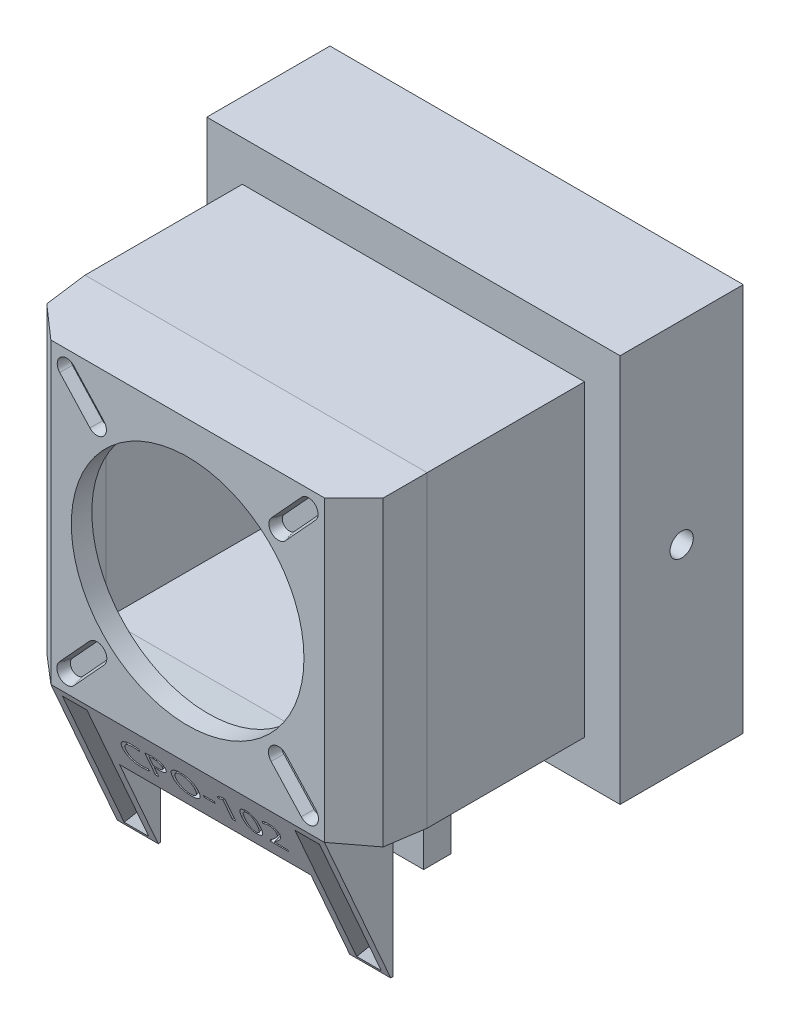
SolidWorks part; units mm, degrees
ref_plane "前视基准面" through (0, 0, 0) normal (0, 0, 1) x (1, 0, 0)
ref_plane "上视基准面" through (0, 0, 0) normal (0, 1, 0) x (1, 0, 0)
ref_plane "右视基准面" through (0, 0, 0) normal (1, 0, 0) x (0, 0, -1)
sketch "草图1" plane through (0, 0, 0) normal (0, 0, 1) x (1, 0, 0)
  line L1 (0, 0) -> (25, 0)
  line L2 (0, 0) -> (0, -22.5)
  line L3 (0, -22.5) -> (25, -22.5)
  line L4 (25, 0) -> (25, -22.5)
  dimension "D1" = 25
  dimension "D2" = 22.5
extrude "凸台-拉伸1" add sketch "草图1" along normal blind 5 draft 4
sketch "草图2" plane through (0, 0, 5) normal (0, 0, 1) x (1, 0, 0)
  line L0 (0.3496, -0.3496) -> (24.6504, -22.1504) construction
  circle A0 centre (12.5, -11.25) radius 8.5
  dimension "D1" = 17
sketch "草图3" plane through (0, 0, 0) normal (0, 0, -1) x (-1, 0, 0)
  line L4 (0, -22.5) -> (0, 0)
  line L5 (0, 0) -> (-25, 0)
  line L6 (-25, 0) -> (-25, -22.5)
  line L7 (-25, -22.5) -> (0, -22.5)
  line L8 (0, -22.5) -> (0, 0)
  line L9 (0, 0) -> (-25, 0)
  line L10 (-25, 0) -> (-25, -22.5)
  line L11 (-25, -22.5) -> (0, -22.5)
  dimension "D1" = 0
extrude "凸台-拉伸2" add sketch "草图3" along normal blind 2.5
chamfer "倒角2" distance 2 angle 45 2 edges at (24.6504, -11.25, 5) (0.3496, -11.25, 5) first distance on face at (24.8252, -11.25, 2.5) first distance on face at (0.1748, -11.25, 2.5)
shell "抽壳1" thickness 1.5 removed face at (12.5, -11.25, -2.5)
extrude "切除-拉伸1" cut sketch "草图2" against normal blind 5
sketch "草图4" plane through (0, 0, 5) normal (0, 0, 1) x (1, 0, 0)
  line L0 (22.4947, -0.3496) -> (2.5053, -22.1504) construction
  line L1 (2.5053, -22.1504) -> (12.5, -11.25) construction
  line L2 (12.5, -11.25) -> (12.5, -3.0139) construction
  line L3 (19.1306, -4.0187) -> (21.3352, -1.6142) construction
  line L4 (18.6184, -3.5491) -> (20.8231, -1.1446)
  line L5 (19.6427, -4.4882) -> (21.8473, -2.0838)
  line L6 (12.5, -11.25) -> (22.4947, -22.1504) construction
  line L7 (19.1306, -18.4813) -> (21.3352, -20.8858) construction
  line L8 (19.6635, -17.9926) -> (21.8682, -20.3971)
  line L9 (18.5976, -18.9701) -> (20.8022, -21.3745)
  line L10 (5.8694, -18.4813) -> (3.6648, -20.8858) construction
  line L11 (5.3365, -17.9926) -> (3.1318, -20.3971)
  line L12 (6.4024, -18.9701) -> (4.1978, -21.3745)
  line L13 (5.8694, -4.0187) -> (3.6648, -1.6142) construction
  line L14 (6.3816, -3.5491) -> (4.1769, -1.1446)
  line L15 (5.3573, -4.4882) -> (3.1527, -2.0838)
  arc A0 (18.6184, -3.5491) -> (19.6427, -4.4882) centre (19.1306, -4.0187) ccw
  arc A1 (21.8473, -2.0838) -> (20.8231, -1.1446) centre (21.3352, -1.6142) ccw
  arc A2 (19.6635, -17.9926) -> (18.5976, -18.9701) centre (19.1306, -18.4813) ccw
  arc A3 (20.8022, -21.3745) -> (21.8682, -20.3971) centre (21.3352, -20.8858) ccw
  arc A4 (5.3365, -17.9926) -> (6.4024, -18.9701) centre (5.8694, -18.4813) cw
  arc A5 (4.1978, -21.3745) -> (3.1318, -20.3971) centre (3.6648, -20.8858) cw
  arc A6 (6.3816, -3.5491) -> (5.3573, -4.4882) centre (5.8694, -4.0187) cw
  arc A7 (3.1527, -2.0838) -> (4.1769, -1.1446) centre (3.6648, -1.6142) cw
  point P8 (20.2329, -2.8164)
  point P17 (20.2329, -19.6836)
  point P24 (4.7671, -19.6836)
  point P31 (4.7671, -2.8164)
extrude "切除-拉伸2" cut sketch "草图4" against normal blind 0.8 draft 13
sketch "草图5" plane through (0, 0, -2.5) normal (0, 0, -1) x (-1, 0, 0)
  line L1 (-23.5, -1.5) -> (-1.5, -1.5)
  line L2 (-23.5, -1.5) -> (-23.5, -21)
  line L3 (-23.5, -21) -> (-1.5, -21)
  line L4 (-25, -22.5) -> (0, -22.5)
  line L5 (0, -22.5) -> (0, 0)
  line L6 (0, 0) -> (-25, 0)
  line L7 (-25, 0) -> (-25, -22.5)
  line L8 (-25, -22.5) -> (0, -22.5)
  line L9 (0, -22.5) -> (0, 0)
  line L10 (0, 0) -> (-25, 0)
  line L11 (-25, 0) -> (-25, -22.5)
  line L12 (-1.5, -1.5) -> (-1.5, -21)
  dimension "D1" = 0
extrude "凸台-拉伸3" add sketch "草图5" along normal blind 10
sketch "草图6" plane through (0, 0, -12.5) normal (0, 0, -1) x (-1, 0, 0)
  line L0 (-27.6, 2.95) -> (2.6, 2.95)
  line L1 (-26.1, 1.45) -> (1.1, 1.45)
  line L2 (-26.1, 1.45) -> (-26.1, -23.95)
  line L3 (-26.1, -23.95) -> (1.1, -23.95)
  line L4 (1.1, 1.45) -> (1.1, -23.95)
  line L5 (-26.1, 1.45) -> (1.1, -23.95) construction
  line L6 (-26.1, -23.95) -> (1.1, 1.45) construction
  line L7 (-23.5, -1.5) -> (-1.5, -1.5)
  line L8 (-23.5, -1.5) -> (-23.5, -21)
  line L9 (-23.5, -21) -> (-1.5, -21)
  line L10 (-1.5, -1.5) -> (-1.5, -21)
  line L11 (2.6, 2.95) -> (2.6, -25.45)
  line L12 (-27.6, -25.45) -> (2.6, -25.45)
  line L13 (-27.6, 2.95) -> (-27.6, -25.45)
  point P0 (-12.5, -11.25)
  line M13 (-25, 0) -> (-25, -22.5)
  line M14 (-25, -22.5) -> (0, -22.5)
  line M15 (0, -22.5) -> (0, 0)
  line M16 (0, 0) -> (-25, 0)
  line M17 (-1.5, -21) -> (-23.5, -21)
  line M18 (-23.5, -21) -> (-23.5, -1.5)
  line M19 (-23.5, -1.5) -> (-1.5, -1.5)
  line M20 (-1.5, -1.5) -> (-1.5, -21)
  dimension "D1" = 25.4
  dimension "D2" = 27.2
  dimension "D3" = 1.5
extrude "凸台-拉伸4" add sketch "草图6" against normal blind 1 contours M16 M13 M14 M15 M20 M17 M18 M19 | L4 L1 L2 L3 M13 M16 M15 M14 | L0 L13 L12 L11 L1 L4 L3 L2 region at (12.5, 2.5354, -12.5) region at (12.5, 1.0778, -12.5) region at (12.5, -0.3363, -12.5)
extrude "凸台-拉伸5" add sketch "草图6<3>" along normal blind 8 contours L0 L13 L12 L11 L1 L4 L3 L2 region at (12.5, 2.5354, -12.5)
sketch "草图6<3>" plane through (0, 0, -12.5) normal (0, 0, -1) x (-1, 0, 0) same geometry as "草图6"
sketch "草图7" plane through (-2.6, 0, 0) normal (-1, 0, 0) x (0, 0, 1)
  line L0 (5, -0.3496) -> (5, -22.1504) construction
  circle A0 centre (-16, -11.25) radius 0.85
  dimension "D2" = 1.7
  dimension "D1" = 21
extrude "切除-拉伸3" cut sketch "草图7" against normal blind 32
sketch "草图8" plane through (25, 0, 0) normal (1, 0, 0) x (0, 0, -1)
  line L0 (-5, -22.1504) -> (0, -33.5)
  line L1 (0, -33.5) -> (0, -22.5)
  line L2 (0, -22.5) -> (-3.0049, -22.2899)
  line L3 (-3.0049, -22.2899) -> (-5, -22.1504)
  dimension "D1" = 11
extrude "凸台-拉伸6" add sketch "草图8" against normal blind 3 from vertex starting at point (22.4947, -22.1504, 5)
extrude "凸台-拉伸7" add sketch "草图8<2>" along normal blind 3 from vertex starting at point (2.5053, -22.1504, 5)
sketch "草图8<2>" plane through (25, 0, 0) normal (1, 0, 0) x (0, 0, -1) same geometry as "草图8"
sketch "草图9" plane through (0, -5.4449, 12.3595) normal (0, -0.4032, 0.9151) x (1, 0, 0)
  line L0 (4.9053, -30.0569) -> (4.9053, -18.8547)
  line L1 (4.9053, -18.8547) -> (3.1053, -18.8547)
  line L2 (3.1053, -18.8547) -> (3.1053, -30.0569)
  line L3 (3.1053, -30.0569) -> (4.9053, -30.0569)
  line L4 (2.5053, -18.2547) -> (2.5053, -30.6569)
  line L5 (2.5053, -30.6569) -> (5.5053, -30.6569)
  line L6 (5.5053, -30.6569) -> (5.5053, -18.2547)
  line L7 (5.5053, -18.2547) -> (2.5053, -18.2547)
  line L8 (2.5053, -18.2547) -> (2.5053, -30.6569)
  line L9 (2.5053, -30.6569) -> (5.5053, -30.6569)
  line L10 (5.5053, -30.6569) -> (5.5053, -18.2547)
  line L11 (5.5053, -18.2547) -> (2.5053, -18.2547)
  line L12 (22.4947, -30.6569) -> (22.4947, -18.2547)
  line L13 (22.4947, -18.2547) -> (19.4947, -18.2547)
  line L14 (19.4947, -18.2547) -> (19.4947, -30.6569)
  line L15 (19.4947, -30.6569) -> (22.4947, -30.6569)
  line L16 (22.4947, -30.6569) -> (22.4947, -18.2547)
  line L17 (22.4947, -18.2547) -> (19.4947, -18.2547)
  line L18 (19.4947, -18.2547) -> (19.4947, -30.6569)
  line L19 (19.4947, -30.6569) -> (22.4947, -30.6569)
  line L20 (20.0947, -18.8547) -> (20.0947, -30.0569)
  line L21 (20.0947, -30.0569) -> (21.8947, -30.0569)
  line L22 (21.8947, -30.0569) -> (21.8947, -18.8547)
  line L23 (21.8947, -18.8547) -> (20.0947, -18.8547)
  dimension "D1" = 0
  dimension "D2" = 0
  dimension "D3" = 0.6
extrude "切除-拉伸4" cut sketch "草图9" against normal blind 1 draft 50 contours L2 L3 L0 L1 | L22 L23 L20 L21 region at (4.0053, -27.8252, 2.5) region at (20.9947, -27.8252, 2.5)
sketch "草图10" plane through (0, -5.4449, 12.3595) normal (0, -0.4032, 0.9151) x (1, 0, 0)
  line L0 (19.4947, -18.2547) -> (19.4947, -30.6569) construction
  line L1 (5.5053, -18.2547) -> (19.4947, -18.2547)
  line L2 (5.5053, -18.2547) -> (5.5053, -23.2547)
  line L3 (5.5053, -23.2547) -> (19.4947, -23.2547)
  line L4 (19.4947, -18.2547) -> (19.4947, -23.2547)
  dimension "D1" = 5
extrude "凸台-拉伸8" add sketch "草图10" along direction (0, 0.0698, 0.9976) on the side against the normal blind 2
sketch "草图11" plane through (0, -5.4449, 12.3595) normal (0, -0.4032, 0.9151) x (1, 0, 0)
  line L0 (5.3793, -22.0122) -> (18.9174, -22.0122) construction
  text T0 "<b>CPO-102</b>" font "@Kozuka Gothic Pro R" height 2
extrude "切除-拉伸5" cut sketch "草图11" against normal blind 1
sketch "草图12" plane through (0, -22.5, 0) normal (0, -1, 0) x (1, 0, 0)
  line L0 (5.5053, 0) -> (2.5053, 0) construction
  line L1 (2.5053, -2.25) -> (5.5053, -2.25)
  line L2 (2.5053, -2.25) -> (2.5053, -4.25)
  line L3 (2.5053, -4.25) -> (5.5053, -4.25)
  line L4 (5.5053, -2.25) -> (5.5053, -4.25)
  line L5 (19.4947, 0) -> (19.4947, -2.25) construction
  line L6 (22.4947, -2.25) -> (22.4947, -4.25)
  line L7 (19.4947, -2.25) -> (19.4947, -4.25)
  line L8 (19.4947, -4.25) -> (22.4947, -4.25)
  line L9 (19.4947, -2.25) -> (22.4947, -2.25)
  dimension "D1" = 2.25
  dimension "D2" = 2
extrude "凸台-拉伸9" add sketch "草图12" along normal blind 5
sketch "草图13" plane through (2.5053, 0, 0) normal (-1, 0, 0) x (0, 0, 1)
  line L0 (0, -33.1576) -> (0.1508, -33.1576)
  line L1 (0, -33.5) -> (0, -22.5) construction
  line L2 (5, -22.1504) -> (0, -33.5) construction
  line L3 (0.1508, -33.1576) -> (0, -33.5)
  line L4 (0, -33.5) -> (0, -33.1576)
extrude "切除-拉伸6" cut sketch "草图13" against normal blind 29
